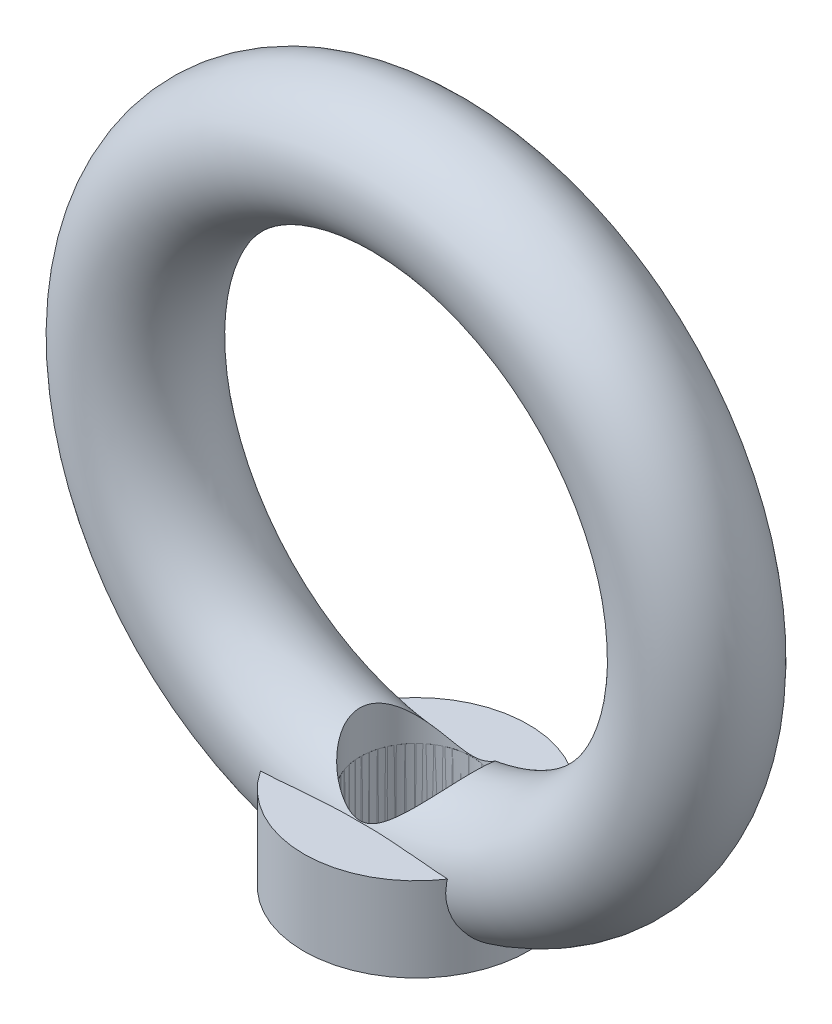
SolidWorks part; units mm, degrees
material "1060 合金"
ref_plane "前视基准面" through (0, 0, 0) normal (0, 0, 1) x (1, 0, 0)
ref_plane "上视基准面" through (0, 0, 0) normal (0, 1, 0) x (1, 0, 0)
ref_plane "右视基准面" through (0, 0, 0) normal (1, 0, 0) x (0, 0, -1)
sketch "草图2" plane through (0, 0, 0) normal (0, 1, 0) x (1, 0, 0)
  circle A0 centre (10, 0) radius 2.25
  dimension "D1" = 4.5
  dimension "D2" = 10
ref_axis "基准轴1" through (0, 0, -2.2) along (0, 0, 1)
revolve "旋转1" add sketch "草图2" angle 360 about axis through (0, 0, -2.2) along (0, 0, 1)
ref_plane "基准面1" through (0, -12, 0) normal (0, 1, 0) x (1, 0, 0)
sketch "草图3" plane through (0, -12, 0) normal (0, 1, 0) x (1, 0, 0)
  circle A0 centre (0, 0) radius 2
  circle A1 centre (0, 0) radius 4
  dimension "D1" = 4
  dimension "D2" = 8
extrude "凸台-拉伸1" add sketch "草图3" along normal blind 3 separate body
extrude "切除-拉伸5" cut sketch "草图3<5>" against normal blind 3 and the other way blind 13 contours A0 region at (0, -12, 0)
sketch "草图3<5>" plane through (0, -12, 0) normal (0, 1, 0) x (1, 0, 0) same geometry as "草图3"
